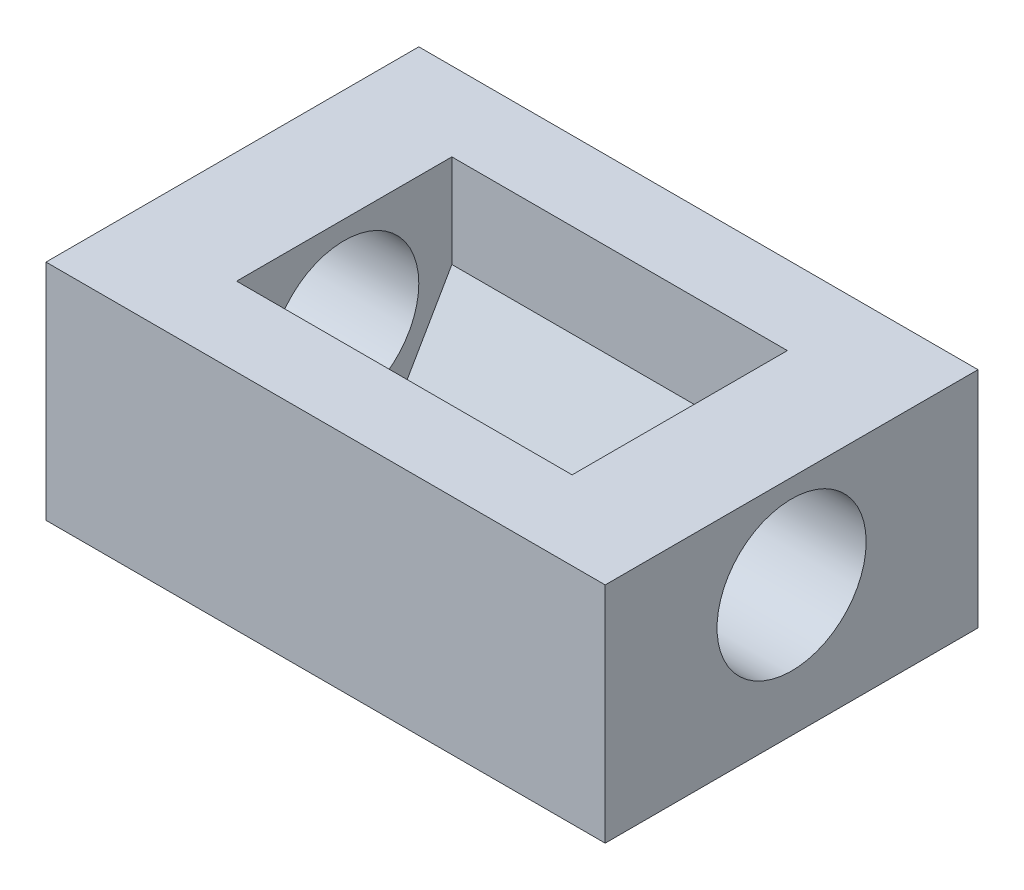
SolidWorks part; units mm, degrees
ref_plane "Front Plane" through (0, 0, 0) normal (0, 0, 1) x (1, 0, 0)
ref_plane "Top Plane" through (0, 0, 0) normal (0, 1, 0) x (1, 0, 0)
ref_plane "Right Plane" through (0, 0, 0) normal (1, 0, 0) x (0, 0, -1)
sketch "Sketch1" plane through (0, 0, 0) normal (0, 1, 0) x (1, 0, 0)
  line L1 (15, -10) -> (-15, -10)
  line L2 (15, -10) -> (15, 10)
  line L3 (15, 10) -> (-15, 10)
  line L4 (-15, -10) -> (-15, 10)
  line L5 (15, -10) -> (-15, 10) construction
  line L6 (15, 10) -> (-15, -10) construction
  point P0 (0, 0)
  dimension "D1" = 30
  dimension "D2" = 20
extrude "Boss-Extrude1" add sketch "Sketch1" along normal blind 12
sketch "Sketch2" plane through (0, 0, 0) normal (1, 0, 0) x (0, 0, -1)
  line L1 (-2.8868, 2) -> (2.8868, 2)
  line L2 (2.8868, 2) -> (5.7735, 7)
  line L6 (-5.7735, 7) -> (-2.8868, 2)
  line L7 (5.7735, 7) -> (3.0311, 11.75) [skipped]
  line L8 (-2.8868, 12) -> (-3.0311, 11.75) [skipped]
  line L9 (2.8868, 12) -> (-2.8868, 12) [skipped]
  line L10 (-5.7735, 7) -> (-5.7735, 12)
  line L11 (-10, 12) -> (10, 12) construction
  line L12 (5.7735, 7) -> (5.7735, 12)
  line L13 (5.7735, 12) -> (-5.7735, 12)
  dimension "D2" = 2
  dimension "D3" = 2.8868
extrude "Cut-Extrude1" cut sketch "Sketch2" against normal blind 9 and the other way blind 9
sketch "Sketch3" plane through (0, 0, 0) normal (1, 0, 0) x (0, 0, -1)
  line L0 (-10, 12) -> (10, 12) construction
  line L1 (-10, 12) -> (-10, 0) construction
  circle A0 centre (0, 7) radius 4
  point P4 (0, 0)
  dimension "D1" = 8
  dimension "D2" = 5
  dimension "D3" = 10
extrude "Cut-Extrude2" cut sketch "Sketch3" against normal through all both and the other way through all
sketch "Sketch4" plane through (0, 12, 0) normal (0, 1, 0) x (1, 0, 0)
  line L0 (0, -10.9943) -> (0, 11.1199) construction
  line L1 (16.6171, 0) -> (-17.8422, 0) construction
  circle A0 centre (-12, 6) radius 2
  dimension "D1" = 4
  dimension "D2" = 6
  dimension "D3" = 12
